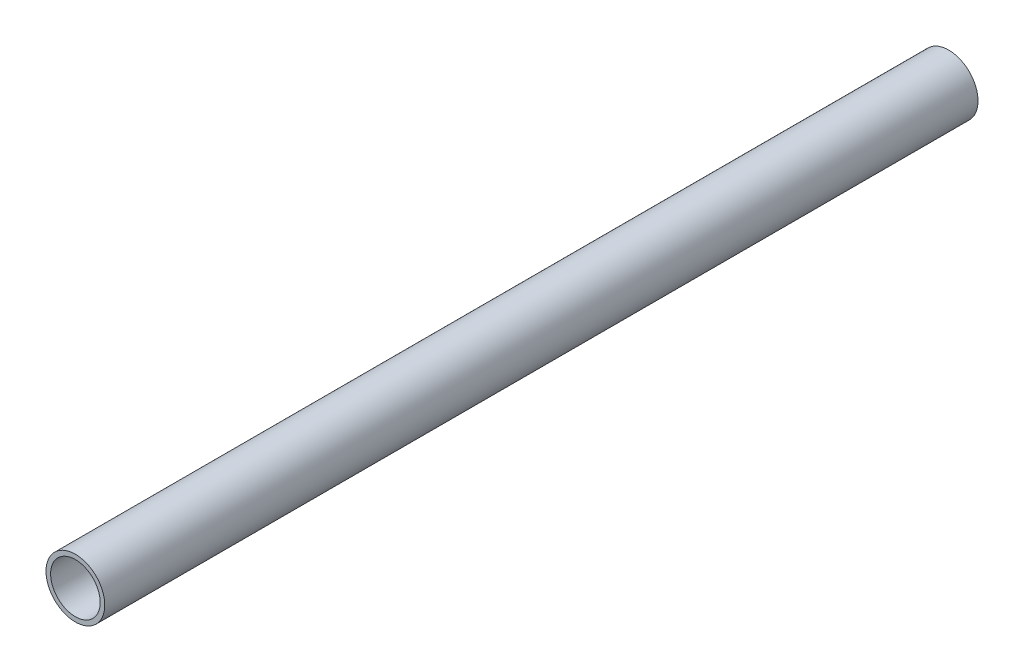
SolidWorks part; units mm, degrees
ref_plane "Front Plane" through (0, 0, 0) normal (0, 0, 1) x (1, 0, 0)
ref_plane "Top Plane" through (0, 0, 0) normal (0, 1, 0) x (1, 0, 0)
ref_plane "Right Plane" through (0, 0, 0) normal (1, 0, 0) x (0, 0, -1)
sketch "Sketch1" plane through (0, 0, 0) normal (0, 0, 1) x (1, 0, 0)
  line L0 (-7.9375, 0) -> (7.9375, 0) construction
  line L1 (0, -7.9375) -> (0, 7.9375) construction
  circle A0 centre (0, 0) radius 7.9375
  circle A1 centre (0, 0) radius 6.6929
  point P4 (0, 0)
  point P9 (0, 0)
  point P10 (6.6929, 0)
  dimension "ID" = 13.3858
  dimension "OD" = 15.875
  dimension "Wall Thickness" = 1.2446
sketch "Sketch2" plane through (0, 0, 0) normal (1, 0, 0) x (0, 0, -1)
  line L0 (117.9656, 7.9375) -> (-117.9656, 7.9375) construction
  line L1 (0, 7.9375) -> (0, -7.9375) construction
  point P3 (-99.7093, 7.9375)
  point P4 (0, 7.9375)
  point P5 (99.7093, 7.9375)
  dimension "Length" = 235.9312
  dimension "D1" = 18.2563
  dimension "D2" = 18.2562
sketch "Sketch3" plane through (0, 0, 0) normal (0, 0, 1) x (1, 0, 0)
  line L0 (0, -7.9375) -> (0, 7.9375) construction
  circle A0 centre (0, 0) radius 7.9375
  circle A1 centre (0, 0) radius 6.6929
  circle A2 centre (0, 0) radius 6.6929 construction
extrude "Boss-Extrude1" add sketch "Sketch3" along normal mid plane 235.9312
equation "\"D1@Boss-Extrude1\" = \"Length@Sketch2\""
equation "\"D1@Sketch2\"=\"OD@Sketch1\"*1.15"
equation "\"D2@Sketch2\"=\"D1@Sketch2\""
